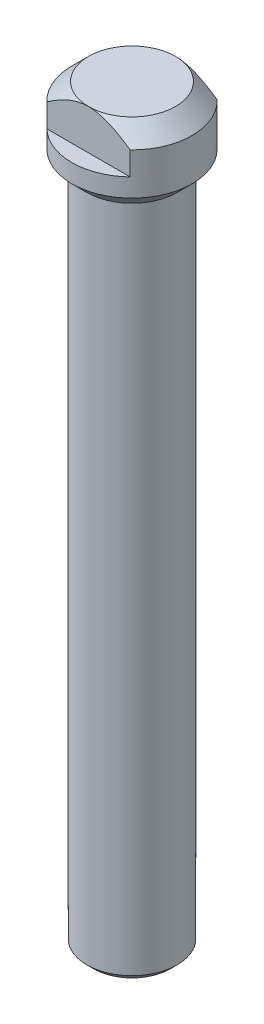
SolidWorks part; units mm, degrees
ref_plane "Спереди" through (0, 0, 0) normal (0, 0, 1) x (1, 0, 0)
ref_plane "Сверху" through (0, 0, 0) normal (0, 1, 0) x (1, 0, 0)
ref_plane "Справа" through (0, 0, 0) normal (1, 0, 0) x (0, 0, -1)
ref_plane "Плоскость4" through (0, 0, 0) normal (0, 0, -1) x (-1, 0, 0)
sketch "Эскиз1" plane through (0, 0, 0) normal (0, 0, -1) x (-1, 0, 0)
  line L0 (-13.5, -224) -> (0, -224)
  line L1 (0, -224) -> (0, 0)
  line L2 (0, 0) -> (-18, 0)
  line L3 (-18, 0) -> (-18, -17.5)
  line L4 (-18, -17.5) -> (-13.5, -22)
  line L5 (-13.5, -22) -> (-13.5, -224)
  line L6 (0, -224) -> (0, 0) construction
revolve "Повернуть1" add sketch "Эскиз1" angle 360 about L6 reverse direction yes
sketch "Эскиз2" plane through (0, 0, 0) normal (0, 1, 0) x (-1, 0, 0)
  line L0 (-12.4499, 13) -> (12.4499, 13)
  arc A0 (12.4499, 13) -> (-12.4499, 13) centre (0, 0) ccw
extrude "Вырез-Вытянуть1" cut sketch "Эскиз2" against normal blind 12
sketch "Эскиз3" plane through (0, 0, 0) normal (0, 1, 0) x (-1, 0, 0)
  line L0 (12.4499, -13) -> (-12.4499, -13)
  arc A0 (-12.4499, -13) -> (12.4499, -13) centre (0, 0) ccw
extrude "Вырез-Вытянуть2" cut sketch "Эскиз3" against normal blind 12
chamfer "Фаска1" distance 5 angle 45 2 edges at (-18, 0, 0) (18, 0, 0)
chamfer "Фаска2" distance 2 angle 45 1 edges at (0, -224, 13.5)
